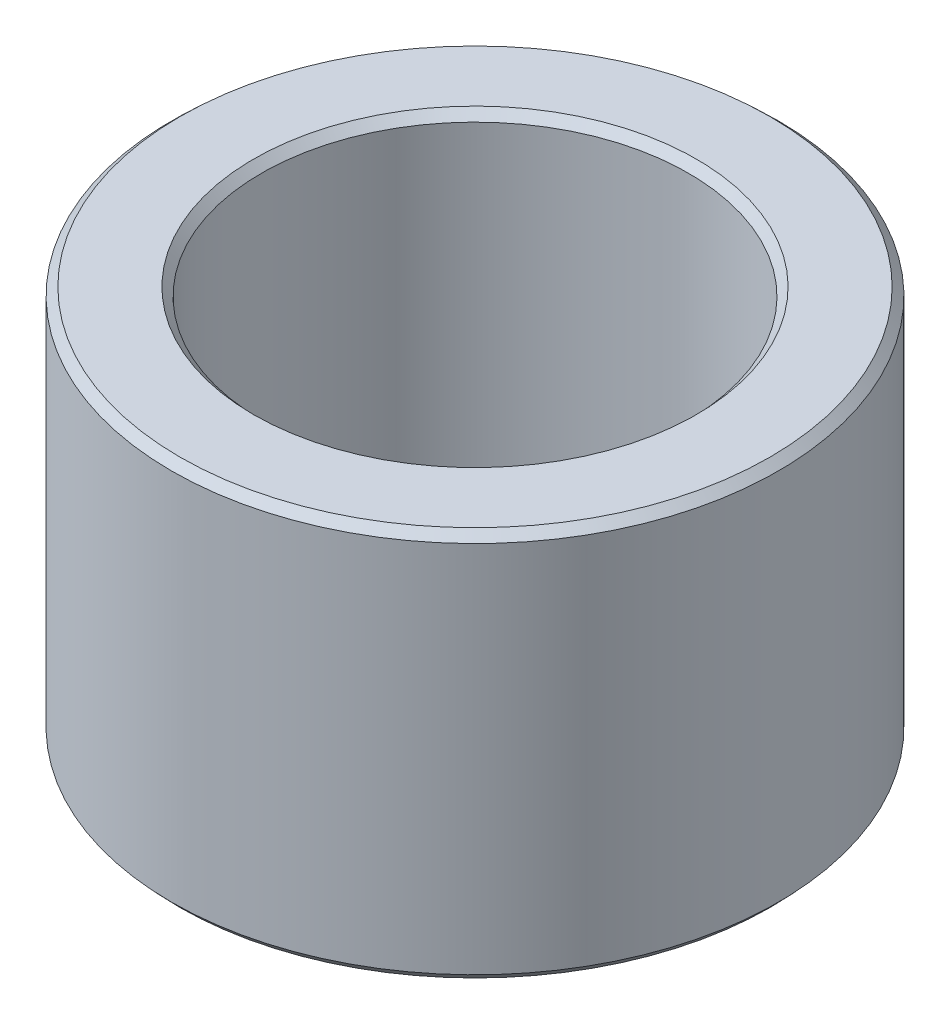
SolidWorks part; units mm, degrees
ref_plane "Front Plane" through (0, 0, 0) normal (0, 0, 1) x (1, 0, 0)
ref_plane "Top Plane" through (0, 0, 0) normal (0, 1, 0) x (1, 0, 0)
ref_plane "Right Plane" through (0, 0, 0) normal (1, 0, 0) x (0, 0, -1)
sketch "Sketch1" plane through (0, 0, 0) normal (0, 1, 0) x (1, 0, 0)
  circle A0 centre (0, 0) radius 12.5
  dimension "SLEEVE_OD" = 25
extrude "Boss-Extrude1" add sketch "Sketch1" along normal blind 16.0576
sketch "Sketch2" plane through (0, 0, 0) normal (0, 1, 0) x (1, 0, 0)
  circle A0 centre (0, 0) radius 8.8004
  dimension "BORE_D" = 17.6008
extrude "Cut-Extrude1" cut sketch "Sketch2" along normal through all
chamfer "Chamfer1" distance 0.3237 angle 46.677 4 edges at (0, 16.0576, 8.8004) (0, 0, 8.8004) (0, 0, 12.5) (0, 16.0576, 12.5) first distance on face at (0, 16.0576, 8.8004) first distance on face at (0, 0, 8.8004) first distance on face at (0, 16.0576, 12.5)
